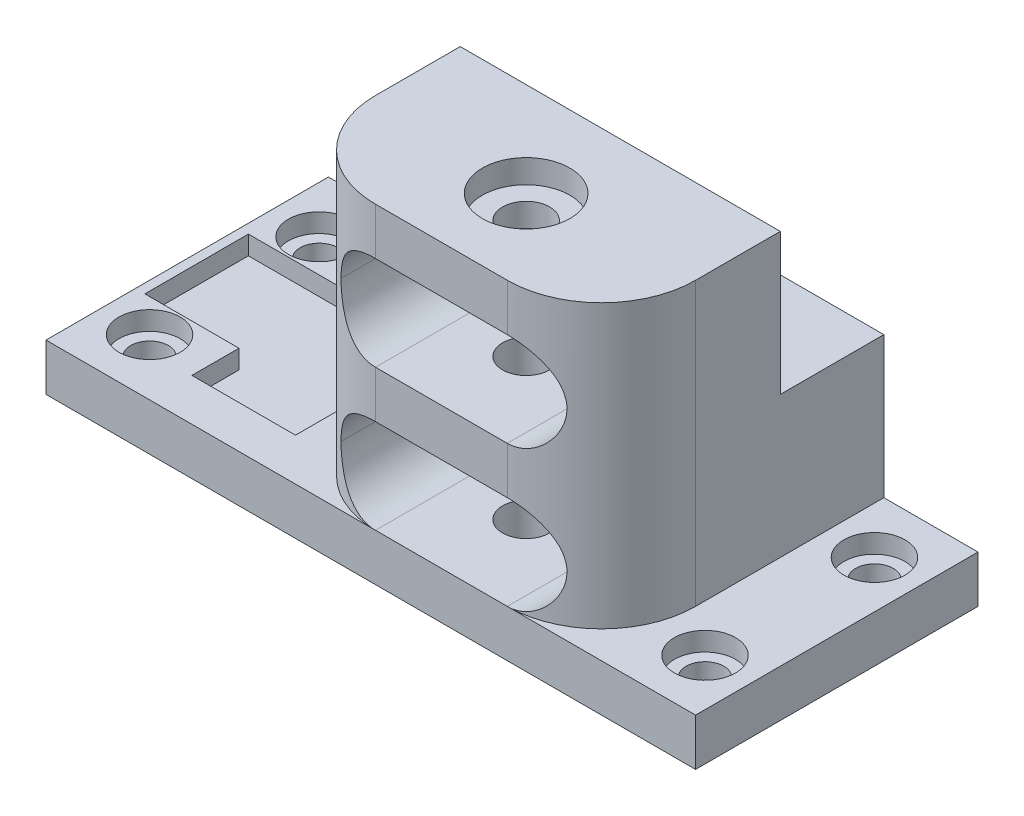
SolidWorks part; units mm, degrees
ref_plane "Alzado" through (0, 0, 0) normal (0, 0, 1) x (1, 0, 0)
ref_plane "Planta" through (0, 0, 0) normal (0, 1, 0) x (1, 0, 0)
ref_plane "Vista lateral" through (0, 0, 0) normal (1, 0, 0) x (0, 0, -1)
sketch "Croquis21" plane through (0, 0, 0) normal (0, 1, 0) x (1, 0, 0)
  line L5 (17.279, 0) -> (51.279, 0)
  line L6 (17.279, 0) -> (17.279, -30)
  line L7 (17.279, -30) -> (51.279, -30)
  line L8 (51.279, 0) -> (51.279, -30)
  dimension "D1" = 34
  dimension "D2" = 30
extrude "Saliente-Extruir4" add sketch "Croquis21" along normal mid plane 35 separate body
sketch "Croquis22" plane through (0, 0, 30) normal (0, 0, 1) x (1, 0, 0)
  line L1 (17.279, 17.5) -> (51.279, 17.5) construction
  line L2 (22.279, 12.5) -> (46.279, 12.5)
  line L3 (22.279, 12.5) -> (22.279, 2.5)
  line L4 (22.279, 2.5) -> (46.279, 2.5)
  line L5 (46.279, 12.5) -> (46.279, 2.5)
  line L6 (51.279, 17.5) -> (51.279, -17.5) construction
  line L9 (34.279, 2.5) -> (34.279, -2.5) construction
  line L10 (22.279, 12.5) -> (46.279, 12.5)
  line L11 (22.279, 12.5) -> (22.279, 2.5)
  line L12 (22.279, 2.5) -> (46.279, 2.5)
  line L13 (46.279, 12.5) -> (46.279, 2.5)
  line L14 (34.279, 0) -> (40.6945, 0) construction
  line L15 (22.279, -2.5) -> (46.279, -2.5)
  line L16 (46.279, -12.5) -> (46.279, -2.5)
  line L17 (22.279, -12.5) -> (46.279, -12.5)
  line L18 (22.279, -12.5) -> (22.279, -2.5)
  line L19 (34.279, -12.5) -> (34.279, -17.5) construction
  line L20 (17.279, -17.5) -> (51.279, -17.5) construction
  dimension "D1" = 10
  dimension "D2" = 24
  dimension "D3" = 5
  dimension "D4" = 5
  dimension "D5" = 5
extrude "Cortar-Extruir17" cut sketch "Croquis22" against normal up to next contours L5 L2 L3 L4 | L18 L17 L16 L15 region at (34.279, 7.5, 30) region at (34.279, -7.5, 30)
sketch "Croquis23" plane through (17.279, 0, 0) normal (-1, 0, 0) x (0, 0, 1)
  line L0 (0, 2.5) -> (11, 2.5)
  line L1 (0, 17.5) -> (30, 17.5) construction
  line L2 (0, 17.5) -> (11, 17.5)
  line L3 (0, 17.5) -> (0, 2.5)
  line L5 (11, 17.5) -> (11, 2.5)
  dimension "D1" = 11
  dimension "D2" = 15
extrude "Cortar-Extruir18" cut sketch "Croquis23" against normal up to next
sketch "Croquis24" plane through (0, 17.5, 0) normal (0, 1, 0) x (1, 0, 0)
  line L0 (17.279, -6) -> (22.279, -6) construction
  line L1 (17.279, 0) -> (17.279, -11) construction
  line L2 (22.279, -6) -> (22.279, 0) construction
  line L3 (51.279, 0) -> (17.279, 0) construction
  line L6 (34.279, -21) -> (34.279, -30) construction
  line L7 (17.279, -30) -> (51.279, -30) construction
  line L11 (34.279, 0) -> (34.279, -3.4347) construction
  circle A0 centre (22.279, -6) radius 2.5 construction
  circle A1 centre (34.279, -21) radius 2.5
  circle A2 centre (46.279, -6) radius 2.5 construction
  point P21 (34.279, -30)
  dimension "D4" = 5
  dimension "D5" = 5
  dimension "D1" = 5
  dimension "D2" = 6
  dimension "D3" = 9
extrude "Cortar-Extruir19" cut sketch "Croquis24" against normal up to surface (35 mm away) up to face at (34.279, -17.5, 15)
sketch "Croquis25" plane through (0, 17.5, 0) normal (0, 1, 0) x (1, 0, 0)
  circle A0 centre (34.279, -21) radius 4.65
  dimension "D1" = 9.3
extrude "Cortar-Extruir20" cut sketch "Croquis25" against normal blind 2.5
sketch "Croquis26" plane through (0, 2.5, 0) normal (0, 1, 0) x (1, 0, 0)
  line L0 (17.279, 0) -> (17.279, -11) construction
  line L7 (27.7638, -6) -> (25.0214, -1.25)
  line L8 (25.0214, -1.25) -> (19.5366, -1.25)
  line L9 (19.5366, -1.25) -> (16.7942, -6)
  line L10 (16.7942, -6) -> (19.5366, -10.75)
  line L11 (19.5366, -10.75) -> (25.0214, -10.75)
  line L12 (25.0214, -10.75) -> (27.7638, -6)
  line L13 (51.7638, -6) -> (49.0214, -1.25)
  line L14 (49.0214, -1.25) -> (43.5366, -1.25)
  line L15 (43.5366, -1.25) -> (40.7942, -6)
  line L16 (40.7942, -6) -> (43.5366, -10.75)
  line L17 (43.5366, -10.75) -> (49.0214, -10.75)
  line L18 (49.0214, -10.75) -> (51.7638, -6)
  line L19 (51.279, -11) -> (51.279, 0) construction
  circle A0 centre (22.279, -6) radius 4.75 construction
  circle A1 centre (46.279, -6) radius 4.75 construction
  dimension "D1" = 9.5
  dimension "D2" = 9.5
  dimension "D3" = 5
  dimension "D4" = 5
fillet "Redondeo2" radius 10 2 edges at (51.279, 0, 30) (17.279, 0, 30)
fillet "Redondeo3" radius 5 8 edges at (46.279, 12.5, 19.8301) (46.279, 2.5, 19.8301) (46.279, -12.5, 14.3301) (22.279, -12.5, 14.3301) (22.279, -2.5, 14.3301) (22.279, 12.5, 19.8301) (22.279, 2.5, 19.8301) (46.279, -2.5, 14.3301)
sketch "Croquis27" plane through (0, -12.5, 0) normal (0, 1, 0) x (1, 0, 0)
  line L0 (34.279, 0) -> (34.279, 12.8238) construction
  line L1 (51.279, 0) -> (17.279, 0) construction
  line L2 (27.279, -30) -> (17.279, -30)
  line L3 (17.279, 0) -> (-7.721, 0)
  line L4 (17.279, 0) -> (17.279, -20)
  line L5 (17.279, -30) -> (-7.721, -30)
  line L6 (-7.721, 0) -> (-7.721, -30)
  line L15 (51.279, 0) -> (51.279, -20)
  line L18 (61.279, 0) -> (61.279, -30)
  line L19 (51.279, 0) -> (61.279, 0)
  line L20 (34.279, 12.8238) -> (-0.221, 12.8238) construction
  line L21 (61.279, -30) -> (41.279, -30)
  arc A0 (17.279, -20) -> (27.279, -30) centre (27.279, -20) ccw construction
  arc A1 (17.279, -20) -> (27.279, -30) centre (27.279, -20) ccw
  circle A2 centre (-2.721, -6) radius 2
  circle A3 centre (-2.721, -24) radius 2
  circle A6 centre (56.279, -6) radius 2
  circle A7 centre (56.279, -24) radius 2
  arc A8 (51.279, -20) -> (41.279, -30) centre (41.279, -20) cw
  point P12 (0, 0)
  dimension "D4" = 4
  dimension "D9" = 4
  dimension "D10" = 4
  dimension "D11" = 4
  dimension "D1" = 10
  dimension "D2" = 6
  dimension "D3" = 5
  dimension "D5" = 34.5
  dimension "D6" = 5
  dimension "D7" = 30
  dimension "D8" = 25
extrude "Saliente-Extruir5" add sketch "Croquis27" against normal blind 5
sketch "Croquis30" plane through (0, -12.5, 0) normal (0, 1, 0) x (1, 0, 0)
  line L0 (-7.721, -28.6236) -> (61.279, -28.6236) construction
  line L1 (61.279, -30) -> (61.279, 0) construction
  line L2 (-7.721, 0) -> (-7.721, -30) construction
  line L3 (-7.721, -15) -> (-6.721, -15) construction
  line L4 (14.279, -7.3133) -> (17.279, -7.3133) construction
  line L5 (3.279, -4.5) -> (14.279, -4.5)
  line L6 (26.779, -28.6236) -> (26.779, -25.5615) construction
  line L7 (3.279, -4.5) -> (3.279, -9.5)
  line L8 (3.279, -25.5) -> (14.279, -25.5)
  line L9 (14.279, -4.5) -> (14.279, -9.5)
  line L10 (17.279, 0) -> (17.279, -11) construction
  line L12 (-6.721, -9.5) -> (3.279, -9.5)
  line L13 (-6.721, -9.5) -> (-6.721, -20.5)
  line L14 (-6.721, -20.5) -> (3.279, -20.5)
  line L15 (14.279, -9.5) -> (14.279, -20.5)
  line L16 (14.279, -20.5) -> (14.279, -25.5)
  line L17 (3.279, -20.5) -> (3.279, -25.5)
  circle A0 centre (-2.721, -6) radius 3.25
  circle A1 centre (-2.721, -24) radius 3.25
  circle A3 centre (56.279, -6) radius 3.25
  circle A4 centre (56.279, -24) radius 3.25
  point P39 (-6.721, -15)
  dimension "D1" = 6.5
  dimension "D2" = 11
  dimension "D3" = 21
  dimension "D4" = 11
  dimension "D5" = 11
  dimension "D6" = 21
extrude "Cortar-Extruir21" cut sketch "Croquis30" against normal blind 2
